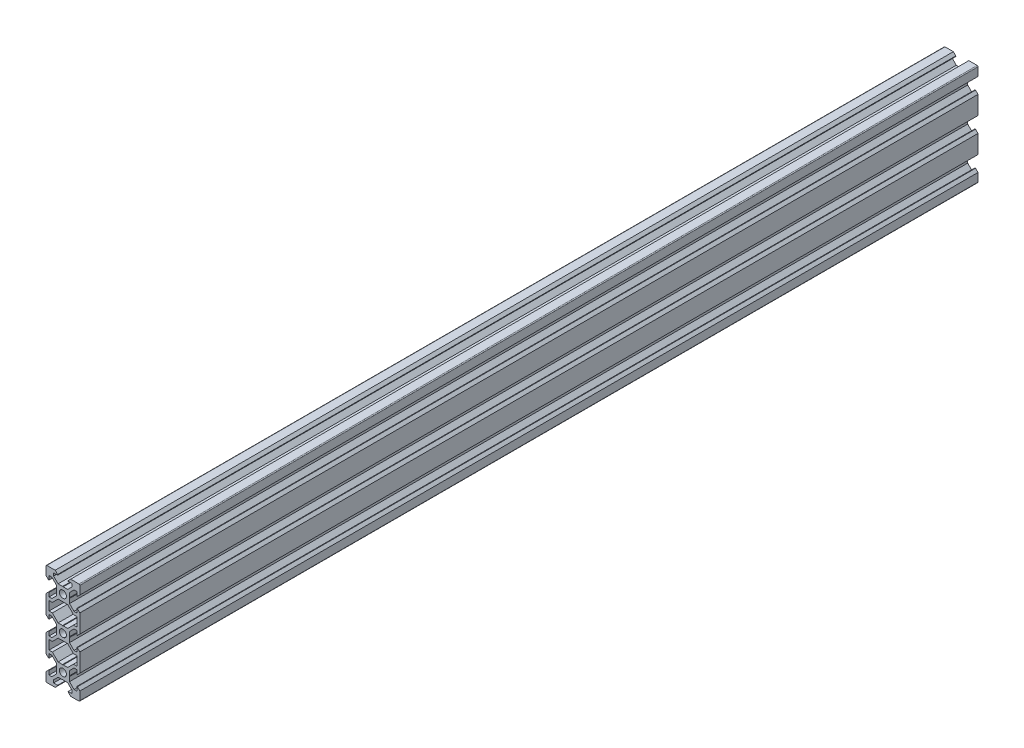
SolidWorks part; units mm, degrees
ref_plane "Plan de face" through (0, 0, 0) normal (0, 0, 1) x (1, 0, 0)
ref_plane "Plan de dessus" through (0, 0, 0) normal (0, 1, 0) x (1, 0, 0)
ref_plane "Plan de droite" through (0, 0, 0) normal (1, 0, 0) x (0, 0, -1)
ref_axis "Axe" through (0, 0, -13.782) along (0, 0, 1)
sketch "Esquisse1" plane through (0, 0, 0) normal (0, 0, 1) x (1, 0, 0)
  line L0 (0, 27.6392) -> (0, -27.6392) construction
  line L1 (-33.6074, 0) -> (33.6074, 0) construction
  line L2 (0, 0) -> (-22.2114, 22.2114) construction
  line L3 (-9.5, 10) -> (-4.58, 10)
  line L4 (-4.58, 10) -> (-3.125, 8.545)
  line L5 (-3.125, 8.545) -> (-3.125, 8.2)
  line L6 (-3.125, 8.2) -> (-5.5, 8.2)
  line L7 (-2.8393, 3.9) -> (-5.5, 6.5607)
  line L8 (-2.8393, 3.9) -> (-0.21, 3.9)
  line L9 (-5.5, 6.5607) -> (-5.5, 8.2)
  line L10 (0, 3.69) -> (0, 2.1)
  line L11 (-3.9, 2.8393) -> (-6.5607, 5.5)
  line L12 (-8.545, 3.125) -> (-8.2, 3.125)
  line L13 (-8.2, 3.125) -> (-8.2, 5.5)
  line L14 (-6.5607, 5.5) -> (-8.2, 5.5)
  line L15 (-10, 4.58) -> (-8.545, 3.125)
  line L16 (-10, 9.5) -> (-10, 4.58)
  line L17 (-0.21, 3.9) -> (0, 3.69)
  line L18 (-3.9, 2.8393) -> (-3.9, 0.21)
  line L19 (-6.2393, -12.7) -> (-8.2, -12.7)
  line L20 (-3.9, 0.21) -> (-3.69, 0)
  line L21 (-0.21, -3.9) -> (0, -3.69)
  line L22 (0, -3.69) -> (0, -2.1)
  line L23 (-6.5607, -5.5) -> (-8.2, -5.5)
  line L24 (-2.8393, -3.9) -> (-0.21, -3.9)
  line L25 (-8.545, -3.125) -> (-8.2, -3.125)
  line L26 (-10, -4.58) -> (-8.545, -3.125)
  line L27 (-8.2, -3.125) -> (-8.2, -5.5)
  line L28 (-2.8393, -3.9) -> (-6.2393, -7.3)
  line L29 (-3.9, -2.8393) -> (-6.5607, -5.5)
  line L30 (-3.9, -2.8393) -> (-3.9, -0.21)
  line L31 (-3.9, -0.21) -> (-3.69, 0)
  line L32 (-6.2393, -7.3) -> (-8.2, -7.3)
  line L33 (-8.2, -7.3) -> (-8.2, -12.7)
  line L34 (-8.2, -10) -> (-10, -10) construction
  line L35 (-10, -15.42) -> (-10, -4.58)
  line L36 (-3.9, -19.79) -> (-3.69, -20)
  line L37 (-3.9, -17.1607) -> (-3.9, -19.79)
  line L38 (-3.9, -17.1607) -> (-6.5607, -14.5)
  line L39 (-2.8393, -16.1) -> (-6.2393, -12.7)
  line L40 (-8.2, -16.875) -> (-8.2, -14.5)
  line L41 (-10, -15.42) -> (-8.545, -16.875)
  line L42 (-8.545, -16.875) -> (-8.2, -16.875)
  line L43 (-2.8393, -16.1) -> (-0.21, -16.1)
  line L44 (-6.5607, -14.5) -> (-8.2, -14.5)
  line L45 (0, -16.31) -> (0, -17.9)
  line L46 (-0.21, -16.1) -> (0, -16.31)
  line L47 (-8.2, -30) -> (-10, -30) construction
  line L48 (-3.69, -20) -> (0, -20) construction
  line L49 (-0.21, -23.9) -> (0, -23.69)
  line L50 (0, -23.69) -> (0, -22.1)
  line L51 (-6.5607, -25.5) -> (-8.2, -25.5)
  line L52 (-2.8393, -23.9) -> (-0.21, -23.9)
  line L53 (-8.545, -23.125) -> (-8.2, -23.125)
  line L54 (-10, -24.58) -> (-8.545, -23.125)
  line L55 (-8.2, -23.125) -> (-8.2, -25.5)
  line L56 (-2.8393, -23.9) -> (-6.2393, -27.3)
  line L57 (-3.9, -22.8393) -> (-6.5607, -25.5)
  line L58 (-3.9, -22.8393) -> (-3.9, -20.21)
  line L59 (-3.9, -20.21) -> (-3.69, -20)
  line L60 (-10, -24.58) -> (-10, -35.42)
  line L61 (-8.2, -32.7) -> (-8.2, -27.3)
  line L62 (-6.2393, -32.7) -> (-8.2, -32.7)
  line L63 (-3.9, -39.79) -> (-3.69, -40)
  line L64 (-3.9, -37.1607) -> (-3.9, -39.79)
  line L65 (-3.9, -37.1607) -> (-6.5607, -34.5)
  line L66 (-2.8393, -36.1) -> (-6.2393, -32.7)
  line L67 (-8.2, -36.875) -> (-8.2, -34.5)
  line L68 (-10, -35.42) -> (-8.545, -36.875)
  line L69 (-8.545, -36.875) -> (-8.2, -36.875)
  line L70 (-2.8393, -36.1) -> (-0.21, -36.1)
  line L71 (-6.5607, -34.5) -> (-8.2, -34.5)
  line L72 (0, -36.31) -> (0, -37.9)
  line L73 (-0.21, -36.1) -> (0, -36.31)
  line L74 (-3.9, -40.21) -> (-3.69, -40)
  line L75 (-6.2393, -27.3) -> (-8.2, -27.3)
  line L76 (-3.9, -42.8393) -> (-3.9, -40.21)
  line L77 (-0.21, -43.9) -> (0, -43.69)
  line L78 (-10, -49.5) -> (-10, -44.58)
  line L79 (-10, -44.58) -> (-8.545, -43.125)
  line L80 (-6.5607, -45.5) -> (-8.2, -45.5)
  line L81 (-8.2, -43.125) -> (-8.2, -45.5)
  line L82 (-8.545, -43.125) -> (-8.2, -43.125)
  line L83 (-3.9, -42.8393) -> (-6.5607, -45.5)
  line L84 (0, -43.69) -> (0, -42.1)
  line L85 (-5.5, -46.5607) -> (-5.5, -48.2)
  line L86 (-2.8393, -43.9) -> (-0.21, -43.9)
  line L87 (-2.8393, -43.9) -> (-5.5, -46.5607)
  line L88 (-3.125, -48.2) -> (-5.5, -48.2)
  line L89 (-3.125, -48.545) -> (-3.125, -48.2)
  line L90 (-4.58, -50) -> (-3.125, -48.545)
  line L91 (-9.5, -50) -> (-4.58, -50)
  arc A0 (0, -2.1) -> (0, 2.1) centre (0, 0) cw
  arc A1 (-9.5, 10) -> (-10, 9.5) centre (-9.5, 9.5) ccw
  arc A2 (0, -37.9) -> (0, -42.1) centre (0, -40) ccw
  arc A3 (-9.5, -50) -> (-10, -49.5) centre (-9.5, -49.5) cw
  arc A4 (0, -17.9) -> (0, -22.1) centre (0, -20) ccw
  point P4 (0, 0)
  point P7 (0, 0)
  point P30 (-10, 10)
  point P60 (0, -20)
  point P111 (-10, -50)
  dimension "D5" = 11
  dimension "D2" = 2.1
  dimension "D3" = 6.25
  dimension "D10" = 0.5
  dimension "D4" = 9.16
  dimension "D6" = 1.5
  dimension "D7" = 1.8
  dimension "D8" = 4.3
  dimension "D9" = 20
  dimension "D11" = 0.42
  dimension "D12" = 10
  dimension "D13" = 1.8
extrude "Boss.-Extru.1" add sketch "Esquisse1" along normal blind 531.13
sketch "Esquisse3" plane through (0, 0, 531.13) normal (0, 0, 1) x (1, 0, 0)
  line L0 (0, 0) -> (-9.8536, 9.8536) construction
  line L1 (-8.2, 8.2) -> (-8.2, 6.57)
  line L2 (-8.2, 6.57) -> (-7.54, 6.57)
  line L3 (-7.54, 6.57) -> (-6.57, 7.54)
  line L4 (-8.2, 3.125) -> (-8.2, 5.5) construction
  line L5 (-6.57, 8.2) -> (-6.57, 7.54)
  line L6 (-8.2, 8.2) -> (-6.57, 8.2)
  line L7 (-5.5, 6.5607) -> (-5.5, 8.2) construction
  line L8 (-3.69, -20) -> (0, -20) construction
  line L9 (-8.2, -48.2) -> (-6.57, -48.2)
  line L10 (-6.57, -48.2) -> (-6.57, -47.54)
  line L11 (-7.54, -46.57) -> (-6.57, -47.54)
  line L12 (-8.2, -46.57) -> (-7.54, -46.57)
  line L13 (-8.2, -48.2) -> (-8.2, -46.57)
  arc A0 (-9.5, 10) -> (-10, 9.5) centre (-9.5, 9.5) ccw construction
  point P13 (-7.055, 7.055)
  point P14 (-6.57, 7.87)
  point P26 (-7.055, -47.055)
  dimension "D1" = 1.07
extrude "Enlèv. mat.-Extru.1" [suppressed] cut sketch "Esquisse3" against normal through all
mirror "Symétrie1" about plane through (0, 3.69, 531.13) normal (-1, 0, 0) of "Enlèv. mat.-Extru.1", "Boss.-Extru.1"
